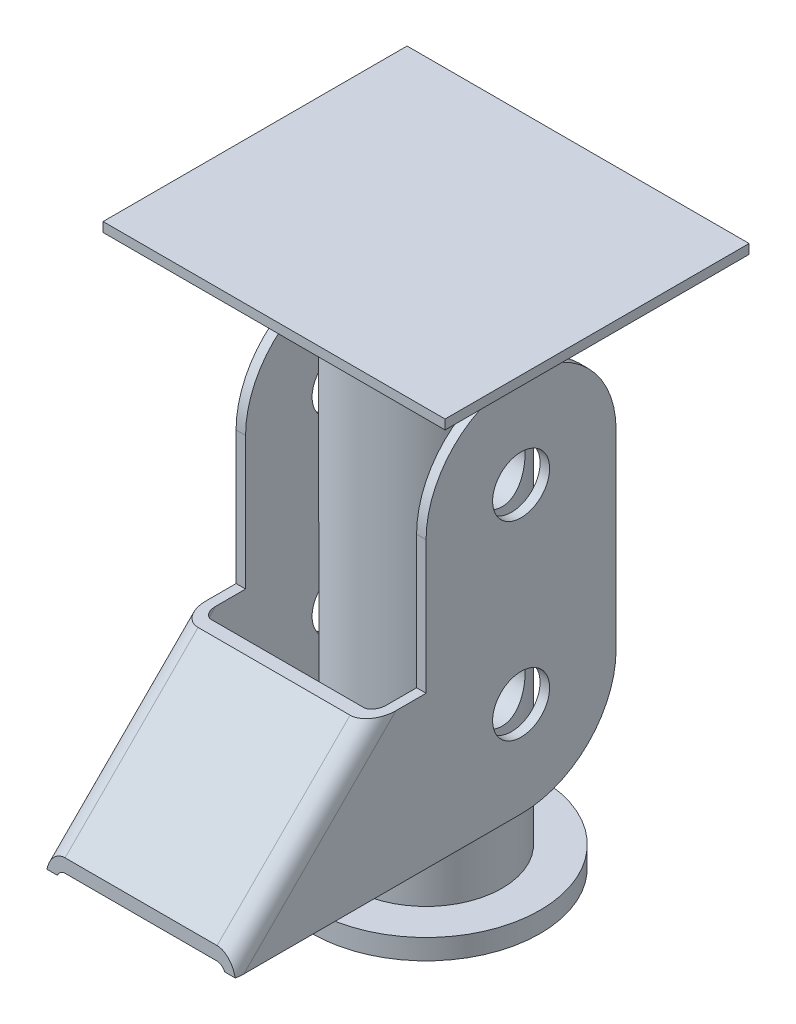
SolidWorks part; units mm, degrees
material "STEEL"
ref_plane "Front Plane" through (0, 0, 0) normal (0, 0, 1) x (1, 0, 0)
ref_plane "Top Plane" through (0, 0, 0) normal (0, 1, 0) x (1, 0, 0)
ref_plane "Right Plane" through (0, 0, 0) normal (1, 0, 0) x (0, 0, -1)
sketch "Sketch1" plane through (0, 0, 0) normal (0, 1, 0) x (1, 0, 0)
  line L0 (-57.15, -50.8) -> (57.15, 50.8) construction
  line L1 (-57.15, 50.8) -> (57.15, 50.8)
  line L2 (-57.15, 50.8) -> (-57.15, -50.8)
  line L3 (-57.15, -50.8) -> (57.15, -50.8)
  line L4 (57.15, 50.8) -> (57.15, -50.8)
  dimension "D1" = 114.3
  dimension "D2" = 101.6
extrude "Extrude1" add sketch "Sketch1" against normal blind 3.175
sketch "Sketch2" plane through (0, 0, 0) normal (0, 1, 0) x (1, 0, 0)
  circle A0 centre (0, 0) radius 25.4
  dimension "D1" = 50.8
extrude "Extrude2" add sketch "Sketch2" against normal blind 189.8015
sketch "Sketch3" plane through (0, 0, 0) normal (1, 0, 0) x (0, 0, -1)
  line L0 (-31.75, -25.4) -> (31.75, -25.4)
  line L1 (31.75, -25.4) -> (31.75, -152.4)
  line L2 (31.75, -152.4) -> (-95.25, -152.4)
  line L3 (-95.25, -152.4) -> (-95.25, -146.05)
  line L4 (-95.25, -146.05) -> (-50.8, -101.6)
  line L5 (-50.8, -101.6) -> (-31.75, -101.6)
  line L6 (-31.75, -101.6) -> (-31.75, -25.4)
  line L7 (50.8, 0) -> (-50.8, 0) construction
  dimension "D1" = 63.5
  dimension "D2" = 50.8
  dimension "D3" = 45
  dimension "D4" = 31.75
  dimension "D5" = 127
  dimension "D6" = 25.4
  dimension "D7" = 127
  dimension "D8" = 6.35
extrude "Extrude3" add sketch "Sketch3" along normal mid plane 63.5 separate body
fillet "Fillet1" radius 31.75 3 edges at (0, -152.4, -31.75) (0, -25.4, -31.75) (0, -25.4, 31.75)
fillet "Fillet2" radius 6.35 2 edges at (-31.75, -123.825, 73.025) (31.75, -123.825, 73.025)
shell "Shell1" thickness 3.175 removed face at (0, -148.5175, 95.25) removed face at (0, -152.4, 62.6281) removed face at (0, -139.8128, -19.1628) removed face at (0, -88.9, -31.75) removed face at (0, -37.9872, -19.1628) removed face at (0, -37.9872, 19.1628) removed face at (0, -79.375, 31.75) removed face at (0, -101.6, 42.0765)
sketch "Sketch4" plane through (-31.75, 0, 0) normal (-1, 0, 0) x (0, 0, 1)
  point P0 (0, -57.15)
  point P1 (0, -120.65)
hole_wizard "3/4 (0.75) Diameter Hole1" positions "3DSketch1" profile "Sketch5" hole size "3/4" standard "Ansi Inch" end condition through all
sketch3d "3DSketch1"
  point P0 (-31.75, -57.15, 0)
  point P3 (-31.75, -120.65, 0)
sketch "Sketch5" plane through (-31.75, -57.15, 0) normal (0, 1, 0) x (0, 0, 1)
  line L0 (0, 0) -> (0, 88.9)
  line L1 (0, 88.9) -> (9.525, 88.9)
  line L2 (9.525, 88.9) -> (9.525, 0)
  line L5 (9.525, 0) -> (0, 0)
  line L11 (0, -6.35) -> (0, 107.95) construction
  dimension "Thru Hole Dia." = 19.05
  dimension "Thru Hole Depth" = 88.9
sketch "Sketch6" plane through (0, -189.8015, 0) normal (0, -1, 0) x (1, 0, 0)
  circle A0 centre (0, 0) radius 38.1
  dimension "D1" = 76.2
extrude "Extrude4" add sketch "Sketch6" against normal blind 12.7
chamfer "Chamfer1" distance 12.7 angle 25 1 edges at (0, -189.8015, -38.1) first distance on face at (0, -189.8015, -38.1)
ref_point "Point1"
